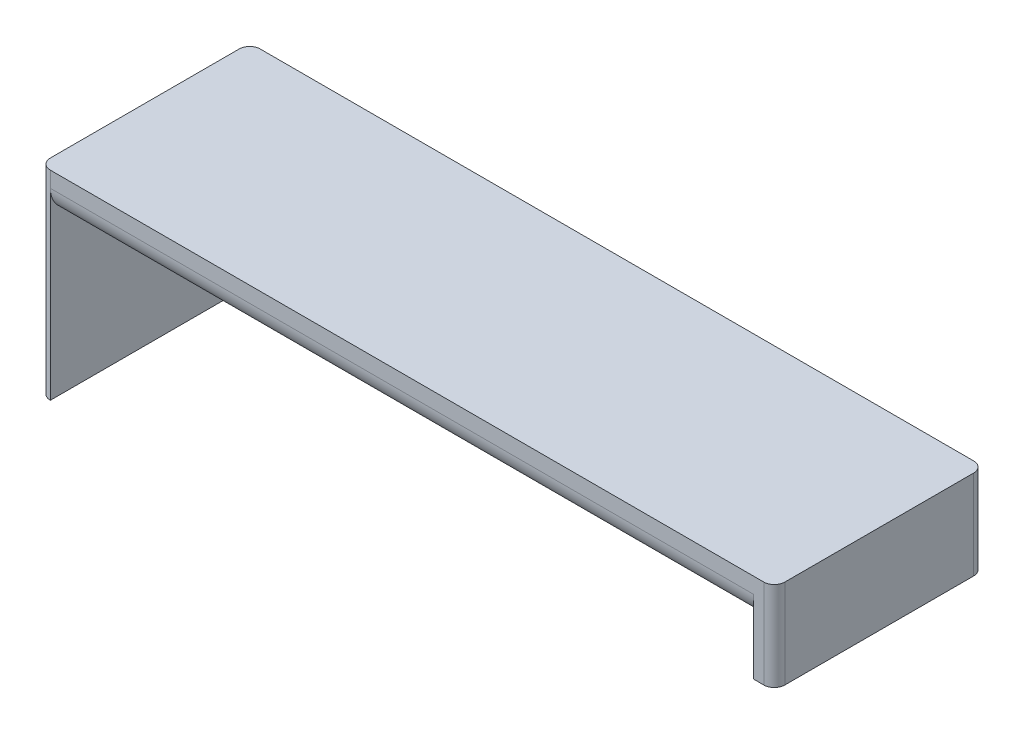
SolidWorks part; units mm, degrees
ref_plane "Front Plane" through (0, 0, 0) normal (0, 0, 1) x (1, 0, 0)
ref_plane "Top Plane" through (0, 0, 0) normal (0, 1, 0) x (1, 0, 0)
ref_plane "Right Plane" through (0, 0, 0) normal (1, 0, 0) x (0, 0, -1)
sketch "Sketch1" plane through (0, 0, 0) normal (0, 1, 0) x (1, 0, 0)
  line L1 (-70, 20) -> (70, 20)
  line L2 (-70, 20) -> (-70, -20)
  line L3 (-70, -20) -> (70, -20)
  line L4 (70, 20) -> (70, -20)
  line L5 (-70, 20) -> (70, -20) construction
  line L6 (-70, -20) -> (70, 20) construction
  line L7 (-70, 20) -> (-68, 20)
  line L8 (-70, 20) -> (-70, -20)
  line L9 (-70, -20) -> (-68, -20)
  line L10 (-68, 20) -> (-68, -20)
  line L11 (-70, 20) -> (-68, -20) construction
  line L12 (-70, -20) -> (-68, 20) construction
  line L13 (70, 20) -> (68, 20)
  line L14 (70, 20) -> (70, -20)
  line L15 (70, -20) -> (68, -20)
  line L16 (68, 20) -> (68, -20)
  line L17 (70, 20) -> (68, -20) construction
  line L18 (70, -20) -> (68, 20) construction
  point P0 (0, 0)
  point P8 (-69, 0)
  point P11 (69, 0)
  dimension "D1" = 140
  dimension "D2" = 40
  dimension "D3" = 2
  dimension "D4" = 2
extrude "Boss-Extrude1" add sketch "Sketch1" along normal blind 8 contours L16 L1 L10 L3 | L1 L16 L3 L4 | L10 L1 L2 L3 region at (-69, 0, 0) region at (0, 0, 0) region at (69, 0, 0)
extrude "Boss-Extrude2" add sketch "Sketch1<3>" against normal blind 9 contours L1 L16 L3 L4 region at (69, 0, 0)
sketch "Sketch1<3>" plane through (0, 0, 0) normal (0, 1, 0) x (1, 0, 0) same geometry as "Sketch1"
sketch "Sketch2" plane through (68, 0, 0) normal (-1, 0, 0) x (0, 0, 1)
  line L0 (-20, 0) -> (20, 0) construction
  line L1 (9.125, 0) -> (-9.125, 0)
  line L2 (9.125, 0) -> (9.125, -9)
  line L3 (9.125, -9) -> (-9.125, -9)
  line L4 (-9.125, 0) -> (-9.125, -9)
  line L5 (9.125, 0) -> (-9.125, -9) construction
  line L6 (9.125, -9) -> (-9.125, 0) construction
  line L7 (-20, -9) -> (-20, 0) construction
  line L8 (9.125, -9) -> (8.525, -9)
  line L9 (9.125, -9) -> (9.125, 0)
  line L10 (9.125, 0) -> (8.525, 0)
  line L11 (8.525, -9) -> (8.525, 0)
  line L12 (9.125, -9) -> (8.525, 0) construction
  line L13 (9.125, 0) -> (8.525, -9) construction
  line L14 (-9.125, -9) -> (-8.525, -9)
  line L15 (-9.125, -9) -> (-9.125, 0)
  line L16 (-9.125, 0) -> (-8.525, 0)
  line L17 (-8.525, -9) -> (-8.525, 0)
  line L18 (-9.125, -9) -> (-8.525, 0) construction
  line L19 (-9.125, 0) -> (-8.525, -9) construction
  line L20 (8.525, -0.6) -> (-8.525, -0.6)
  line L21 (8.525, -0.6) -> (8.525, 0)
  line L22 (8.525, 0) -> (-8.525, 0)
  line L23 (-8.525, -0.6) -> (-8.525, 0)
  line L24 (8.525, -0.6) -> (-8.525, 0) construction
  line L25 (8.525, 0) -> (-8.525, -0.6) construction
  line L26 (-9.125, -9) -> (-20, -9)
  line L27 (-9.125, -9) -> (-9.125, 0)
  line L28 (-9.125, 0) -> (-20, 0)
  line L29 (-20, -9) -> (-20, 0)
  line L30 (-9.125, -9) -> (-20, 0) construction
  line L31 (-9.125, 0) -> (-20, -9) construction
  line L33 (9.125, -9) -> (20, -9)
  line L34 (9.125, -9) -> (9.125, 0)
  line L35 (9.125, 0) -> (20, 0)
  line L36 (20, -9) -> (20, 0)
  line L37 (9.125, -9) -> (20, 0) construction
  line L38 (9.125, 0) -> (20, -9) construction
  point P4 (0, -4.5)
  point P7 (0, 0)
  point P11 (8.825, -4.5)
  point P14 (-8.825, -4.5)
  point P18 (0, -0.3)
  point P20 (-14.5625, -4.5)
  point P25 (14.5625, -4.5)
  line M3 (20, 0) -> (-20, 0)
  line M4 (-20, 0) -> (-20, -9)
  line M6 (20, -9) -> (20, 0)
  dimension "D1" = 18.25
  dimension "D2" = 9
  dimension "D3" = 0.6
  dimension "D4" = 0.6
  dimension "D5" = 0.6
extrude "Boss-Extrude3" add sketch "Sketch2" along normal blind 1 contours L2 L33 M6 M3 | L26 L4 M3 M4 region at (68, -4.5, 14.5625) region at (68, -4.5, -14.5625)
extrude "Boss-Extrude4" add sketch "Sketch2<3>" along normal blind 1 from surface contours L11 L3 L2 M3 | L2 L33 M6 M3 | L20 L11 L1 L17 | L3 L17 L4 M3 | L26 L4 M3 M4 region at (68, -4.5, 8.825) region at (68, -4.5, 14.5625) region at (68, -0.3, 0) region at (68, -4.5, -8.825) region at (68, -4.5, -14.5625) starting at face at (67, -4.5, 14.5625)
sketch "Sketch2<3>" plane through (68, 0, 0) normal (-1, 0, 0) x (0, 0, 1) same geometry as "Sketch2"
ref_plane "Plane1" through (64, 0, 0) normal (-1, 0, 0) x (0, 0, 1)
extrude "Boss-Extrude5" add sketch "Sketch1<4>" against normal blind 30 contours L10 L1 L2 L3 region at (-69, 0, 0)
sketch "Sketch1<4>" plane through (0, 0, 0) normal (0, 1, 0) x (1, 0, 0) same geometry as "Sketch1"
sketch "Sketch3" plane through (64, 0, 0) normal (-1, 0, 0) x (0, 0, 1)
  line L0 (0, 0) -> (0, -8) construction
  line L1 (11.4197, -4) -> (-11.4197, -4)
  line L2 (-11.4197, -4) -> (-11.4197, 0)
  line L3 (-11.4197, 0) -> (0, 0)
  line L4 (0, 0) -> (11.4197, 0)
  line L5 (-20, 0) -> (20, 0) construction
  line L6 (11.4197, 0) -> (11.4197, -4)
  circle A0 centre (0, -8) radius 12.1
  point P5 (0, 0)
  point P7 (0, -4)
  point P12 (-1.4598, -12.0116)
  point P13 (0, 0)
  point P14 (0, 0)
  point P15 (0, -12.1)
  point P16 (11.5105, 0)
  point P17 (0, 0)
  point P18 (0, 0)
  point P19 (0, -10.4932)
  point P20 (0, -7.2884)
  point P21 (0, 0)
  point P22 (0, -4.0126)
  dimension "D1" = 24.2
  dimension "D2" = 8
extrude "Cut-Extrude1" cut sketch "Sketch3" along normal up to surface (132 mm away) contours L1 A0 | L4 L0 L1 A0 | L0 L3 A0 L1 | L4 A0 L3 region at (64, -2.0741, 5.2329) region at (64, -2.0741, -5.2329) region at (64, 1.6664, 0) region at (64, -11.055, 0) up to face at (-68, -15, 0)
fillet "Fillet1" radius 5 2 edges at (-1, 0, 20) (-1, 0, -20)
fillet "Fillet2" radius 2 4 edges at (-70, -11, 20) (-70, -11, -20) (70, -0.5, 20) (70, -0.5, -20)
extrude "Boss-Extrude6" add sketch "Sketch3<3>" along normal up to surface and the other way up to surface contours A0 L3 L2 | A0 L6 L4 region at (64, -1.2253, 10.6935) region at (64, -1.2253, -10.6935) up to face at (-68, -5.9964, 0) other way up to face at (66, -2.9271, 0)
sketch "Sketch3<3>" plane through (64, 0, 0) normal (-1, 0, 0) x (0, 0, 1) same geometry as "Sketch3"
fillet "Fillet3" radius 0.5 2 edges at (-1, -4, -11.4197) (-1, -4, 11.4197)
fillet "Fillet4" radius 1 2 edges at (-1, 0, -11.4197) (-1, 0, 11.4197)
fillet "Fillet5" radius 1 1 edges at (64, 0, 0)
